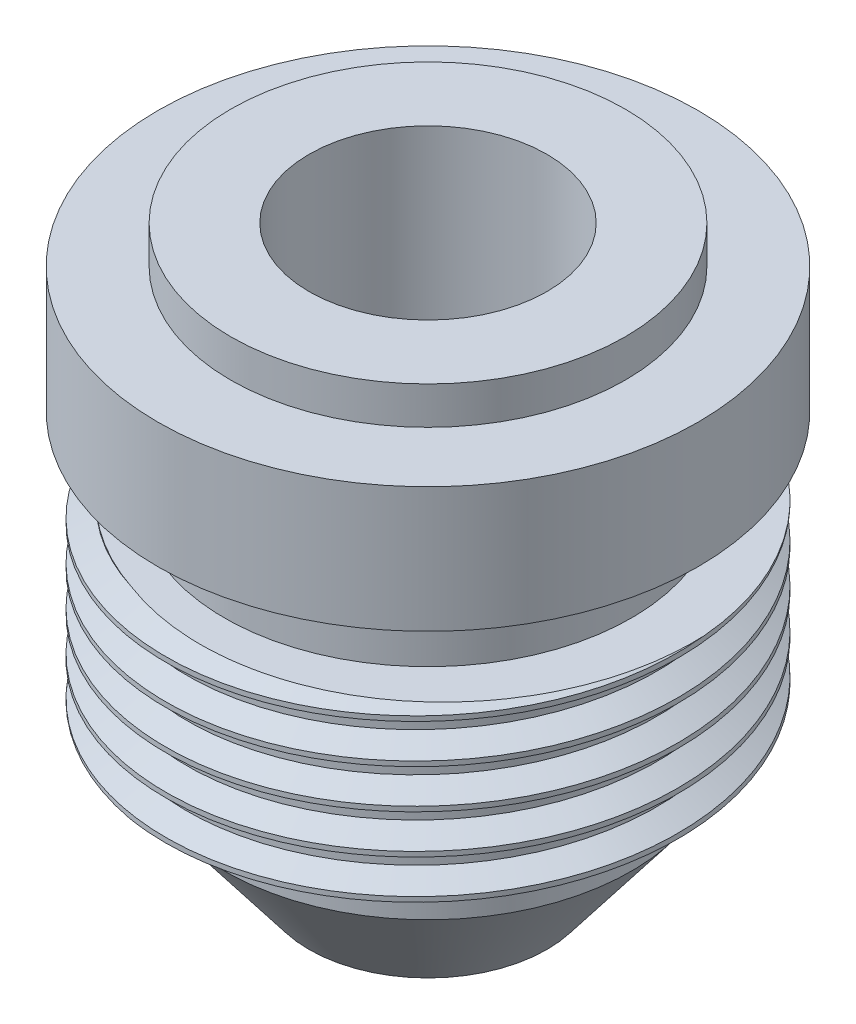
SolidWorks part; units mm, degrees
ref_plane "Front Plane" through (0, 0, 0) normal (0, 0, 1) x (1, 0, 0)
ref_plane "Top Plane" through (0, 0, 0) normal (0, 1, 0) x (1, 0, 0)
ref_plane "Right Plane" through (0, 0, 0) normal (1, 0, 0) x (0, 0, -1)
sketch "Sketch1" plane through (0, 0, 0) normal (0, 0, 1) x (1, 0, 0)
  line L0 (0, 0) -> (0, 55136.1981) construction
  line L1 (4.826, 0) -> (8.001, 0)
  line L2 (8.001, 0) -> (8.001, -1.524)
  line L3 (8.001, -1.524) -> (10.9537, -1.524)
  line L4 (10.9537, -1.524) -> (10.9537, -6.604)
  line L5 (10.9537, -6.604) -> (8.255, -6.604)
  line L6 (8.255, -6.604) -> (8.255, -9.7536)
  line L7 (8.255, -18.6452) -> (4.826, -23.114)
  line L10 (4.826, -23.114) -> (4.826, 0)
  line L11 (8.255, -9.7536) -> (9.525, -9.7536)
  line L12 (9.525, -9.7536) -> (9.525, -16.764)
  line L13 (9.525, -16.764) -> (8.255, -16.764)
  line L14 (8.255, -16.764) -> (8.255, -18.6452)
  point P12 (0, 0)
  point P13 (0, 0)
  point P17 (8.255, -7.706)
  point P18 (0, 0)
  dimension "D1" = 16.002
  dimension "D2" = 37.5
  dimension "D3" = 21.9075
  dimension "D4" = 16.51
  dimension "D5" = 5.08
  dimension "D6" = 6.35
  dimension "D7" = 16.51
  dimension "D8" = 19.05
  dimension "D9" = 1.524
  dimension "D10" = 13.3604
  dimension "D11" = 9.652
revolve "Revolve1" add sketch "Sketch1" angle 360 about L0
cosmetic thread "Cosmetic Thread1" parameters "D2"=13.6812
thread "Thread2" pitch 1.5875 method extrude trim with start face yes trim with end face yes profile "Thread Profile2" start angle 0, offset 1.27, length 8.382, pitch 1.5875, diameter 19.05
ref_plane "Plane2" through (-9.525, -8.4836, 0) normal (0, 0, 1) x (-1, 0, 0)
sketch "Thread Profile2" plane through (-9.525, -8.4836, 0) normal (0, 0, 1) x (-1, 0, 0)
  line L0 (0, 0) -> (0, 1.5875) construction
  line L1 (0, 0) -> (0.8593, 0.4961)
  line L2 (0.8593, 0.4961) -> (0.8593, 0.6945)
  line L3 (0.8593, 0.6945) -> (0, 1.1906)
  line L4 (0.8593, 0.5953) -> (0, 0.5953) construction
  line L11 (0, 0) -> (0, 1.1906)
  point P2 (0, 0)
  dimension "Pitch" = 1.5875
  dimension "Profile_Angle" = 60
  dimension "Profile_Land" = 0.1984
  dimension "Profile_Height" = 0.8593
